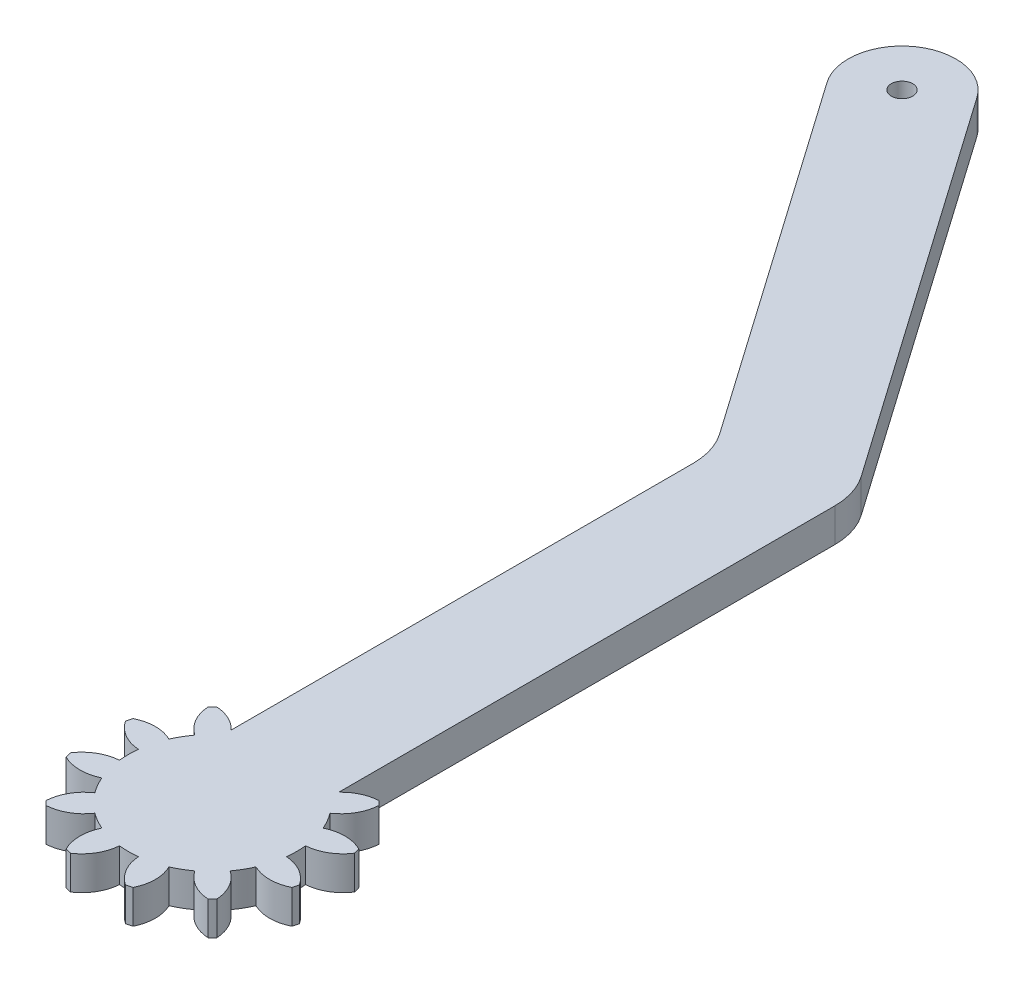
SolidWorks part; units mm, degrees
ref_plane "Front Plane" through (0, 0, 0) normal (0, 0, 1) x (1, 0, 0)
ref_plane "Top Plane" through (0, 0, 0) normal (0, 1, 0) x (1, 0, 0)
ref_plane "Right Plane" through (0, 0, 0) normal (1, 0, 0) x (0, 0, -1)
sketch "Sketch1" plane through (0, 0, 0) normal (0, 1, 0) x (1, 0, 0)
  line L1 (8, 9.6047) -> (8, 87.6625)
  line L2 (8, 149.6047) -> (-8, 149.6047) construction
  line L3 (-8, 149.6047) -> (-8, 82.6177) construction
  line L4 (0, 0) -> (0, 47.5503) construction
  line L5 (-8, 82.6177) -> (-51.6918, 145.0161)
  line L6 (-51.6918, 145.0161) -> (-38.5854, 154.1933)
  line L7 (-38.5854, 154.1933) -> (8, 87.6625)
  line L8 (-8, 82.6177) -> (-8, 9.6047)
  line L9 (8, 87.6625) -> (8, 149.6047) construction
  arc A0 (-8, 9.6047) -> (8, 9.6047) centre (0, 0) ccw
  point P1 (-45.1386, 149.6047)
  dimension "D1" = 25
  dimension "D2" = 16
  dimension "D3" = 140
  dimension "D4" = 16
  dimension "D5" = 145
  dimension "D6" = 66.987
extrude "Boss-Extrude1" add sketch "Sketch1" along normal blind 5
fillet "Fillet1" 2 edges at (-51.6918, 2.5, -145.0161) (-38.5854, 2.5, -154.1933) type full round first side face at (-29.8459, 2.5, -113.8169) second side face at (-15.2927, 2.5, -120.9279) middle face at (-45.1386, 2.5, -149.6047)
fillet "Fillet2" radius 10 2 edges at (8, 2.5, -87.6625) (-8, 2.5, -82.6177)
sketch "Sketch2" plane through (0, 5, 0) normal (0, 1, 0) x (1, 0, 0)
  circle A0 centre (-40.55, 143.0515) radius 1.6
  dimension "D1" = 3.2
extrude "Cut-Extrude2" cut sketch "Sketch2" against normal through all contours A0
sketch "Sketch5" plane through (0, 5, 0) normal (0, 1, 0) x (1, 0, 0)
  arc A0 (-12.0517, -12.6888) -> (-7.1035, -9.5148) centre (-12.4017, -6.699) ccw
  arc A1 (-7.1035, -9.5148) -> (-4.6884, -10.9092) centre (0, 0) ccw
  arc A2 (-4.6884, -10.9092) -> (-4.963, -16.7815) centre (0.3993, -14.0897) ccw
  arc A3 (-4.963, -16.7815) -> (-4.0927, -17.0147) centre (0, 0) ccw
  arc A4 (-4.0927, -17.0147) -> (-1.3944, -11.7918) centre (-7.3907, -12.0024) ccw
  arc A5 (-1.3944, -11.7918) -> (1.3944, -11.7918) centre (0, 0) ccw
  arc A6 (1.3944, -11.7918) -> (4.0927, -17.0147) centre (7.3907, -12.0024) ccw
  arc A7 (4.0927, -17.0147) -> (4.963, -16.7815) centre (0, 0) ccw
  arc A8 (4.963, -16.7815) -> (4.6884, -10.9092) centre (-0.3993, -14.0897) ccw
  arc A9 (4.6884, -10.9092) -> (7.1035, -9.5148) centre (0, 0) ccw
  arc A10 (7.1035, -9.5148) -> (12.0517, -12.6888) centre (12.4017, -6.699) ccw
  arc A11 (12.0517, -12.6888) -> (12.6888, -12.0517) centre (0, 0) ccw
  arc A12 (12.6888, -12.0517) -> (9.5148, -7.1035) centre (6.699, -12.4017) ccw
  arc A13 (9.5148, -7.1035) -> (10.9092, -4.6884) centre (0, 0) ccw
  arc A14 (10.9092, -4.6884) -> (16.7815, -4.963) centre (14.0897, 0.3993) ccw
  arc A15 (16.7815, -4.963) -> (17.0147, -4.0927) centre (0, 0) ccw
  arc A16 (17.0147, -4.0927) -> (11.7918, -1.3944) centre (12.0024, -7.3907) ccw
  arc A17 (11.7918, -1.3944) -> (11.7918, 1.3944) centre (0, 0) ccw
  arc A18 (11.7918, 1.3944) -> (17.0147, 4.0927) centre (12.0024, 7.3907) ccw
  arc A19 (17.0147, 4.0927) -> (16.7815, 4.963) centre (0, 0) ccw
  arc A20 (16.7815, 4.963) -> (10.9092, 4.6884) centre (14.0897, -0.3993) ccw
  arc A21 (10.9092, 4.6884) -> (9.5148, 7.1035) centre (0, 0) ccw
  arc A22 (9.5148, 7.1035) -> (12.6888, 12.0517) centre (6.699, 12.4017) ccw
  arc A23 (12.6888, 12.0517) -> (12.0517, 12.6888) centre (0, 0) ccw
  arc A24 (12.0517, 12.6888) -> (7.1035, 9.5148) centre (12.4017, 6.699) ccw
  arc A25 (7.1035, 9.5148) -> (4.6884, 10.9092) centre (0, 0) ccw
  arc A26 (4.6884, 10.9092) -> (4.963, 16.7815) centre (-0.3993, 14.0897) ccw
  arc A27 (4.963, 16.7815) -> (4.0927, 17.0147) centre (0, 0) ccw
  arc A28 (4.0927, 17.0147) -> (1.3944, 11.7918) centre (7.3907, 12.0024) ccw
  arc A29 (1.3944, 11.7918) -> (-1.3944, 11.7918) centre (0, 0) ccw
  arc A30 (-1.3944, 11.7918) -> (-4.0927, 17.0147) centre (-7.3907, 12.0024) ccw
  arc A31 (-4.0927, 17.0147) -> (-4.963, 16.7815) centre (0, 0) ccw
  arc A32 (-4.963, 16.7815) -> (-4.6884, 10.9092) centre (0.3993, 14.0897) ccw
  arc A33 (-4.6884, 10.9092) -> (-7.1035, 9.5148) centre (0, 0) ccw
  arc A34 (-7.1035, 9.5148) -> (-12.0517, 12.6888) centre (-12.4017, 6.699) ccw
  arc A35 (-12.0517, 12.6888) -> (-12.6888, 12.0517) centre (0, 0) ccw
  arc A36 (-12.6888, 12.0517) -> (-9.5148, 7.1035) centre (-6.699, 12.4017) ccw
  arc A37 (-9.5148, 7.1035) -> (-10.9092, 4.6884) centre (0, 0) ccw
  arc A38 (-10.9092, 4.6884) -> (-16.7815, 4.963) centre (-14.0897, -0.3993) ccw
  arc A39 (-16.7815, 4.963) -> (-17.0147, 4.0927) centre (0, 0) ccw
  arc A40 (-17.0147, 4.0927) -> (-11.7918, 1.3944) centre (-12.0024, 7.3907) ccw
  arc A41 (-11.7918, 1.3944) -> (-11.7918, -1.3944) centre (0, 0) ccw
  arc A42 (-11.7918, -1.3944) -> (-17.0147, -4.0927) centre (-12.0024, -7.3907) ccw
  arc A43 (-17.0147, -4.0927) -> (-16.7815, -4.963) centre (0, 0) ccw
  arc A44 (-16.7815, -4.963) -> (-10.9092, -4.6884) centre (-14.0897, 0.3993) ccw
  arc A45 (-10.9092, -4.6884) -> (-9.5148, -7.1035) centre (0, 0) ccw
  arc A46 (-9.5148, -7.1035) -> (-12.6888, -12.0517) centre (-6.699, -12.4017) ccw
  arc A47 (-12.6888, -12.0517) -> (-12.0517, -12.6888) centre (0, 0) ccw
extrude "Boss-Extrude3" add sketch "Sketch5" against normal blind 5
